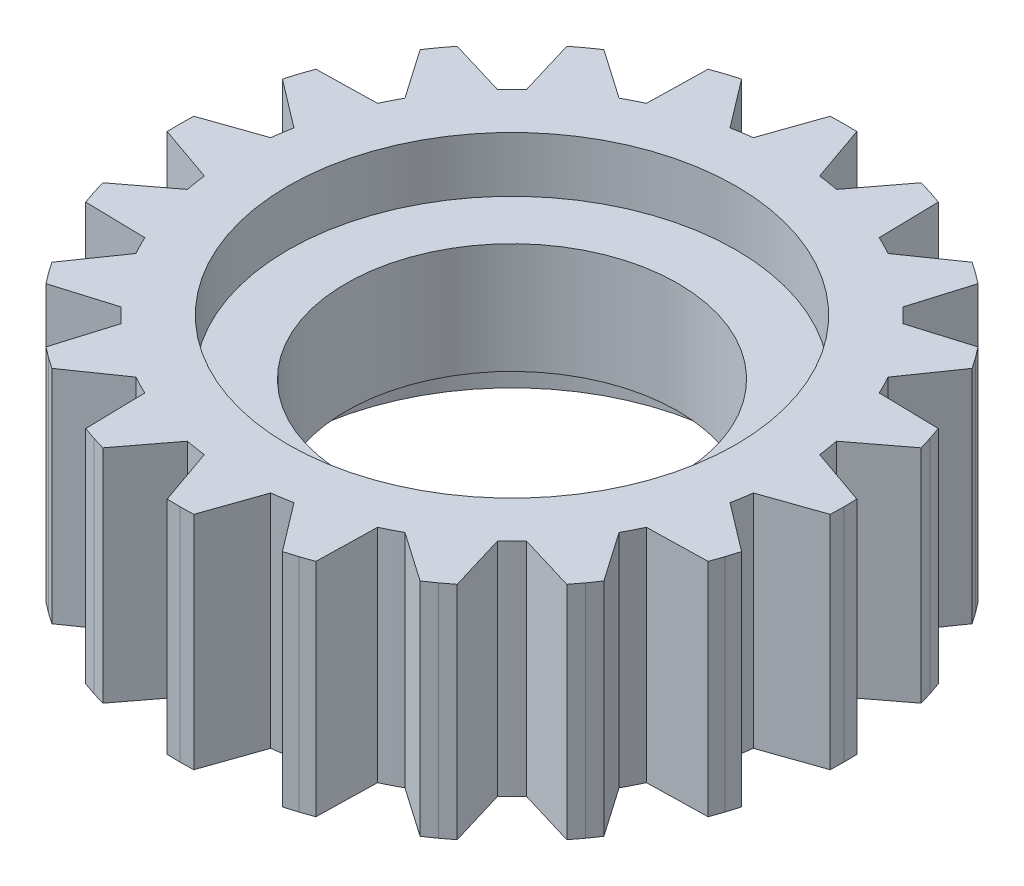
SolidWorks part; units mm, degrees
ref_plane "Front Plane" through (0, 0, 0) normal (0, 0, 1) x (1, 0, 0)
ref_plane "Top Plane" through (0, 0, 0) normal (0, 1, 0) x (1, 0, 0)
ref_plane "Right Plane" through (0, 0, 0) normal (1, 0, 0) x (0, 0, -1)
sketch "Sketch1" plane through (0, 0, 0) normal (0, 1, 0) x (1, 0, 0)
  line L0 (0, 0) -> (25, 0) construction
  line L2 (30, 0) -> (29.976, 1.1998)
  line L3 (29.976, 1.1998) -> (24.8193, 3)
  line L4 (30, 0) -> (29.976, -1.1998)
  line L5 (29.976, -1.1998) -> (24.8193, -3)
  line L7 (28.8796, -8.1221) -> (24.5317, -4.8164)
  line L8 (28.1381, -10.4041) -> (22.6776, -10.5228)
  line L11 (28.5317, -9.2705) -> (28.1381, -10.4041)
  line L12 (24.9563, -16.6488) -> (21.8426, -12.1614)
  line L13 (23.5459, -18.5901) -> (18.3159, -17.0155)
  line L16 (24.2705, -17.6336) -> (23.5459, -18.5901)
  line L17 (18.5901, -23.5459) -> (17.0155, -18.3159)
  line L18 (16.6488, -24.9563) -> (12.1614, -21.8426)
  line L21 (17.6336, -24.2705) -> (16.6488, -24.9563)
  line L22 (10.4041, -28.1381) -> (10.5228, -22.6776)
  line L23 (8.1221, -28.8796) -> (4.8164, -24.5317)
  line L26 (9.2705, -28.5317) -> (8.1221, -28.8796)
  line L27 (1.1998, -29.976) -> (3, -24.8193)
  line L28 (-1.1998, -29.976) -> (-3, -24.8193)
  line L31 (0, -30) -> (-1.1998, -29.976)
  line L32 (-8.1221, -28.8796) -> (-4.8164, -24.5317)
  line L33 (-10.4041, -28.1381) -> (-10.5228, -22.6776)
  line L36 (-9.2705, -28.5317) -> (-10.4041, -28.1381)
  line L37 (-16.6488, -24.9563) -> (-12.1614, -21.8426)
  line L38 (-18.5901, -23.5459) -> (-17.0155, -18.3159)
  line L41 (-17.6336, -24.2705) -> (-18.5901, -23.5459)
  line L42 (-23.5459, -18.5901) -> (-18.3159, -17.0155)
  line L43 (-24.9563, -16.6488) -> (-21.8426, -12.1614)
  line L46 (-24.2705, -17.6336) -> (-24.9563, -16.6488)
  line L47 (-28.1381, -10.4041) -> (-22.6776, -10.5228)
  line L48 (-28.8796, -8.1221) -> (-24.5317, -4.8164)
  line L51 (-28.5317, -9.2705) -> (-28.8796, -8.1221)
  line L52 (-29.976, -1.1998) -> (-24.8193, -3)
  line L53 (-29.976, 1.1998) -> (-24.8193, 3)
  line L56 (-30, 0) -> (-29.976, 1.1998)
  line L57 (-28.8796, 8.1221) -> (-24.5317, 4.8164)
  line L58 (-28.1381, 10.4041) -> (-22.6776, 10.5228)
  line L61 (-28.5317, 9.2705) -> (-28.1381, 10.4041)
  line L62 (-24.9563, 16.6488) -> (-21.8426, 12.1614)
  line L63 (-23.5459, 18.5901) -> (-18.3159, 17.0155)
  line L66 (-24.2705, 17.6336) -> (-23.5459, 18.5901)
  line L67 (-18.5901, 23.5459) -> (-17.0155, 18.3159)
  line L68 (-16.6488, 24.9563) -> (-12.1614, 21.8426)
  line L71 (-17.6336, 24.2705) -> (-16.6488, 24.9563)
  line L72 (-10.4041, 28.1381) -> (-10.5228, 22.6776)
  line L73 (-8.1221, 28.8796) -> (-4.8164, 24.5317)
  line L76 (-9.2705, 28.5317) -> (-8.1221, 28.8796)
  line L77 (-1.1998, 29.976) -> (-3, 24.8193)
  line L78 (1.1998, 29.976) -> (3, 24.8193)
  line L81 (0, 30) -> (1.1998, 29.976)
  line L82 (8.1221, 28.8796) -> (4.8164, 24.5317)
  line L83 (10.4041, 28.1381) -> (10.5228, 22.6776)
  line L86 (9.2705, 28.5317) -> (10.4041, 28.1381)
  line L87 (16.6488, 24.9563) -> (12.1614, 21.8426)
  line L88 (18.5901, 23.5459) -> (17.0155, 18.3159)
  line L91 (17.6336, 24.2705) -> (18.5901, 23.5459)
  line L92 (23.5459, 18.5901) -> (18.3159, 17.0155)
  line L93 (24.9563, 16.6488) -> (21.8426, 12.1614)
  line L96 (24.2705, 17.6336) -> (24.9563, 16.6488)
  line L97 (28.1381, 10.4041) -> (22.6776, 10.5228)
  line L98 (28.8796, 8.1221) -> (24.5317, 4.8164)
  line L101 (28.5317, 9.2705) -> (28.8796, 8.1221)
  line L102 (28.5317, -9.2705) -> (28.8796, -8.1221)
  line L103 (24.2705, -17.6336) -> (24.9563, -16.6488)
  line L104 (17.6336, -24.2705) -> (18.5901, -23.5459)
  line L105 (9.2705, -28.5317) -> (10.4041, -28.1381)
  line L106 (0, -30) -> (1.1998, -29.976)
  line L107 (-9.2705, -28.5317) -> (-8.1221, -28.8796)
  line L108 (-17.6336, -24.2705) -> (-16.6488, -24.9563)
  line L109 (-24.2705, -17.6336) -> (-23.5459, -18.5901)
  line L110 (-28.5317, -9.2705) -> (-28.1381, -10.4041)
  line L111 (-30, 0) -> (-29.976, -1.1998)
  line L112 (-28.5317, 9.2705) -> (-28.8796, 8.1221)
  line L113 (-24.2705, 17.6336) -> (-24.9563, 16.6488)
  line L114 (-17.6336, 24.2705) -> (-18.5901, 23.5459)
  line L115 (-9.2705, 28.5317) -> (-10.4041, 28.1381)
  line L116 (0, 30) -> (-1.1998, 29.976)
  line L117 (9.2705, 28.5317) -> (8.1221, 28.8796)
  line L118 (17.6336, 24.2705) -> (16.6488, 24.9563)
  line L119 (24.2705, 17.6336) -> (23.5459, 18.5901)
  line L120 (28.5317, 9.2705) -> (28.1381, 10.4041)
  circle A0 centre (0, 0) radius 15
  circle A1 centre (0, 0) radius 20.25
  arc A2 (-21.8426, 12.1614) -> (-22.6776, 10.5228) centre (0, 0) ccw
  arc A3 (-17.0155, 18.3159) -> (-18.3159, 17.0155) centre (0, 0) ccw
  arc A4 (-10.5228, 22.6776) -> (-12.1614, 21.8426) centre (0, 0) ccw
  arc A5 (-3, 24.8193) -> (-4.8164, 24.5317) centre (0, 0) ccw
  arc A6 (4.8164, 24.5317) -> (3, 24.8193) centre (0, 0) ccw
  arc A7 (12.1614, 21.8426) -> (10.5228, 22.6776) centre (0, 0) ccw
  arc A8 (18.3159, 17.0155) -> (17.0155, 18.3159) centre (0, 0) ccw
  arc A9 (22.6776, 10.5228) -> (21.8426, 12.1614) centre (0, 0) ccw
  arc A10 (24.8193, 3) -> (24.5317, 4.8164) centre (0, 0) ccw
  arc A11 (24.5317, -4.8164) -> (24.8193, -3) centre (0, 0) ccw
  arc A12 (21.8426, -12.1614) -> (22.6776, -10.5228) centre (0, 0) ccw
  arc A13 (17.0155, -18.3159) -> (18.3159, -17.0155) centre (0, 0) ccw
  arc A14 (10.5228, -22.6776) -> (12.1614, -21.8426) centre (0, 0) ccw
  arc A15 (3, -24.8193) -> (4.8164, -24.5317) centre (0, 0) ccw
  arc A16 (-4.8164, -24.5317) -> (-3, -24.8193) centre (0, 0) ccw
  arc A17 (-12.1614, -21.8426) -> (-10.5228, -22.6776) centre (0, 0) ccw
  arc A18 (-18.3159, -17.0155) -> (-17.0155, -18.3159) centre (0, 0) ccw
  arc A19 (-22.6776, -10.5228) -> (-21.8426, -12.1614) centre (0, 0) ccw
  arc A20 (-24.8193, -3) -> (-24.5317, -4.8164) centre (0, 0) ccw
  arc A21 (-24.5317, 4.8164) -> (-24.8193, 3) centre (0, 0) ccw
  point P4 (24.8193, 0)
  point P128 (0, 0)
  point P167 (0, 0)
  dimension "D1" = 20
  dimension "D2" = 50
  dimension "D3" = 40.5
  dimension "D4" = 30
  dimension "D5" = 30
  dimension "D6" = 6
  dimension "D7" = 2.3995
  dimension "D8" = 30
  dimension "D10" = 1.2
  dimension "D9" = 20
extrude "Boss-Extrude1" add sketch "Sketch1" along normal mid plane 20 contours L57 A21 L53 L56 L111 L52 A20 L48 L51 L110 L47 A19 L43 L46 L109 L42 A18 L38 L41 L108 L37 A17 L33 L36 L107 L32 A16 L28 L31 L106 L27 A15 L23 L26 L105 L22 A14 L18 L21 L104 L17 A13 L13 L16 L103 L12 A12 L8 L11 L102 L7 region at (29.1396, 0, 0.5829)
extrude "Boss-Extrude2" add sketch "Sketch1<3>" along normal mid plane 10 contours A0 A1 region at (-19.6772, 0, 0)
sketch "Sketch1<3>" plane through (0, 0, 0) normal (0, 1, 0) x (1, 0, 0) same geometry as "Sketch1"
